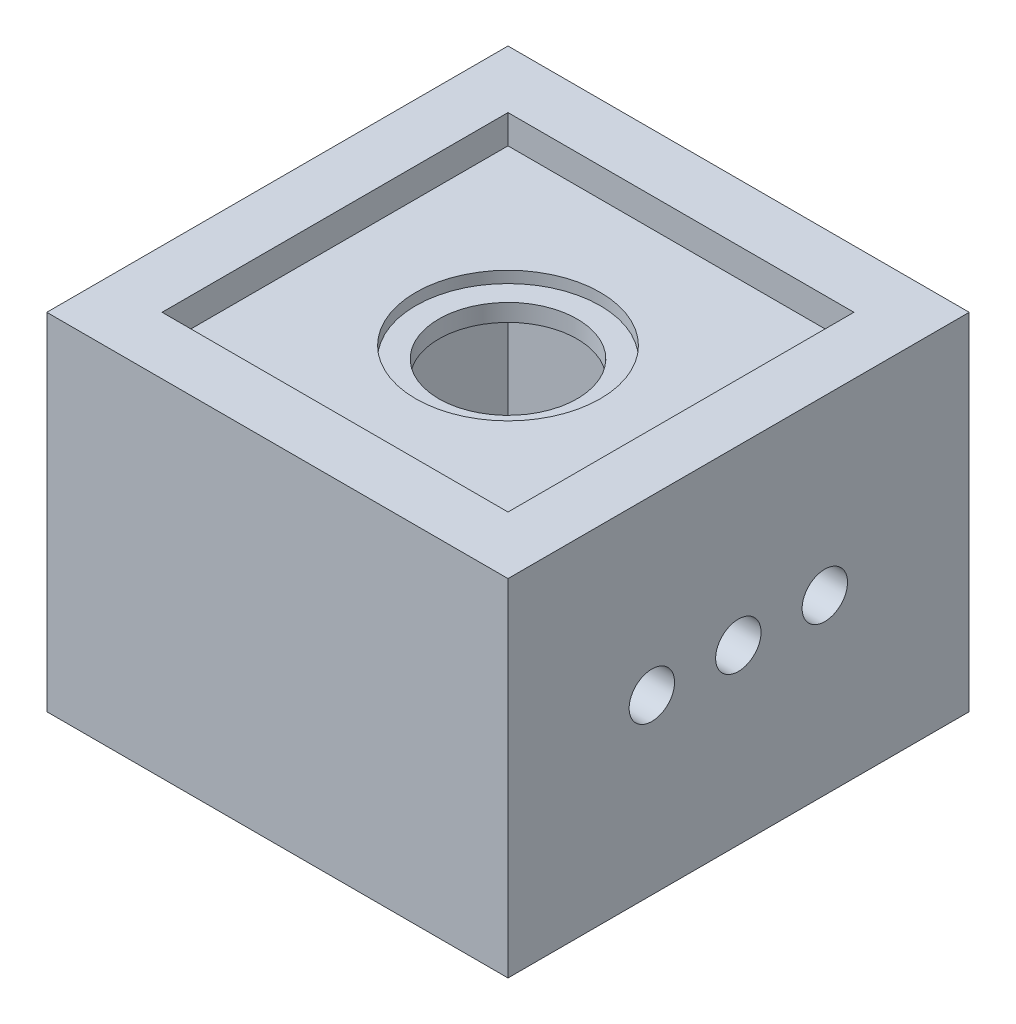
SolidWorks part; units mm, degrees
ref_plane "Front Plane" through (0, 0, 0) normal (0, 0, 1) x (1, 0, 0)
ref_plane "Top Plane" through (0, 0, 0) normal (0, 1, 0) x (1, 0, 0)
ref_plane "Right Plane" through (0, 0, 0) normal (1, 0, 0) x (0, 0, -1)
sketch "Sketch1" plane through (0, 0, 0) normal (0, 1, 0) x (1, 0, 0)
  line L1 (-38.1, -38.1) -> (38.1, -38.1)
  line L2 (-38.1, -38.1) -> (-38.1, 38.1)
  line L3 (-38.1, 38.1) -> (38.1, 38.1)
  line L4 (38.1, -38.1) -> (38.1, 38.1)
  line L5 (-38.1, -38.1) -> (38.1, 38.1) construction
  line L6 (-38.1, 38.1) -> (38.1, -38.1) construction
  line L7 (-50.8, -50.8) -> (50.8, -50.8)
  line L8 (-50.8, -50.8) -> (-50.8, 50.8)
  line L9 (-50.8, 50.8) -> (50.8, 50.8)
  line L10 (50.8, -50.8) -> (50.8, 50.8)
  line L11 (-50.8, -50.8) -> (50.8, 50.8) construction
  line L12 (-50.8, 50.8) -> (50.8, -50.8) construction
  point P0 (0, 0)
  point P6 (0, 0)
  dimension "D1" = 76.2
  dimension "D2" = 76.2
  dimension "D3" = 101.6
  dimension "D4" = 101.6
extrude "Boss-Extrude1" add sketch "Sketch1" along normal blind 76.2
sketch "Sketch2" plane through (0, 76.2, 0) normal (0, 1, 0) x (1, 0, 0)
  line L1 (-38.1, -38.1) -> (38.1, -38.1)
  line L2 (-38.1, -38.1) -> (-38.1, 38.1)
  line L3 (-38.1, 38.1) -> (38.1, 38.1)
  line L4 (38.1, -38.1) -> (38.1, 38.1)
  line L5 (-38.1, -38.1) -> (38.1, 38.1) construction
  line L6 (-38.1, 38.1) -> (38.1, -38.1) construction
  circle A0 centre (0, 0) radius 15.24
  point P0 (0, 0)
  dimension "D1" = 30.48
extrude "Boss-Extrude2" add sketch "Sketch2" against normal blind 6.35 from offset 6.35 offset against normal yes
sketch "Sketch3" plane through (0, 69.85, 0) normal (0, 1, 0) x (1, 0, 0)
  circle A0 centre (0, 0) radius 20.32
  dimension "D1" = 40.64
extrude "Cut-Extrude2" cut sketch "Sketch3" against normal blind 2.54
sketch "Sketch4" plane through (50.8, 0, 0) normal (1, 0, 0) x (0, 0, -1)
  line L0 (-50.8, 76.2) -> (50.8, 76.2) construction
  line L1 (50.8, 76.2) -> (50.8, 0) construction
  line L2 (-50.8, 76.2) -> (50.8, 76.2) construction
  line L3 (50.8, 0) -> (50.8, 76.2) construction
  line L4 (-19.1107, 38.1) -> (18.9893, 38.1)
  circle A0 centre (-19.1107, 38.1) radius 5
  circle A1 centre (-0.0607, 38.1) radius 5
  circle A2 centre (18.9893, 38.1) radius 5
  point P8 (-0.0607, 38.1)
  point P12 (-0.0607, 38.1)
extrude "Cut-Extrude3" cut sketch "Sketch4" against normal up to surface (12.7 mm away) contours A0 | L4 A1 | L4 A1 | A2 region at (50.8, 42.9586, -18.9893) region at (50.8, 40.2221, 0.0607) region at (50.8, 35.9779, 0.0607) region at (50.8, 38.1, 23.9693) up to face at (38.1, 31.75, 0)
